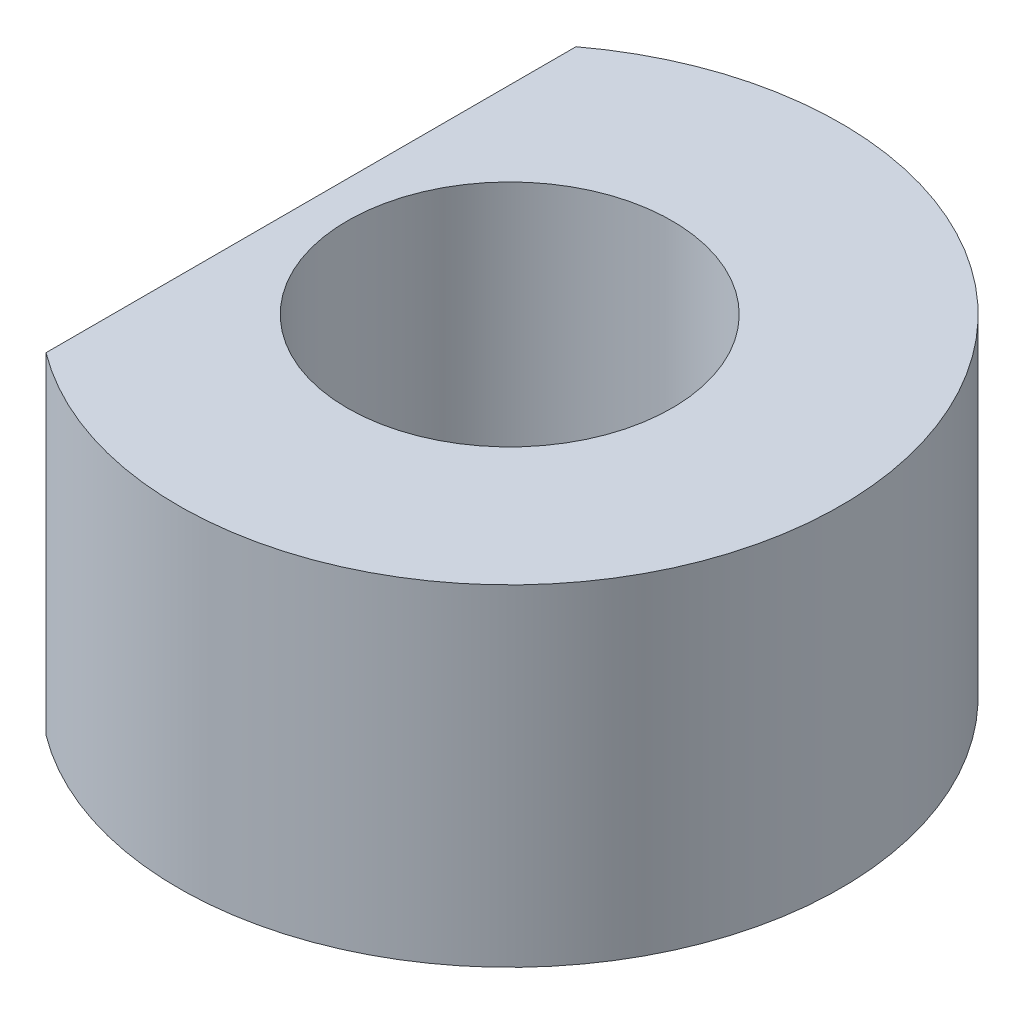
SolidWorks part; units mm, degrees
ref_plane "Front Plane" through (0, 0, 0) normal (0, 0, 1) x (1, 0, 0)
ref_plane "Top Plane" through (0, 0, 0) normal (0, 1, 0) x (1, 0, 0)
ref_plane "Right Plane" through (0, 0, 0) normal (1, 0, 0) x (0, 0, -1)
sketch "Sketch1" plane through (0, 0, 0) normal (0, 1, 0) x (1, 0, 0)
  line L0 (-3, 4) -> (-3, -4)
  arc A0 (-3, -4) -> (-3, 4) centre (0, 0) ccw
  dimension "D1" = 10
  dimension "D2" = 3
base flange "Base-Flange1" sketch "Sketch1" thickness 5 reverse thickness direction no parameters "D1"=0.7366
sketch "Sketch7" plane through (0, 0, 0) normal (0, 1, 0) x (1, 0, 0)
  circle A0 centre (0, 0) radius 2.45
  dimension "D1" = 4.9
extrude "Cut-Extrude1" cut sketch "Sketch7" against normal through all normal cut yes
sketch "Bend-Lines1" plane through (0, 0, 0) normal (0, 1, 0) x (1, 0, 0)
sketch "Bounding-Box1" plane through (0, 0, 0) normal (0, 1, 0) x (1, 0, 0)
sheet metal parameters "Sheet-Metal1" thickness 5 parameters "D1"=0.7366
flat pattern "Flat-Pattern1"
sketch "Bend-Lines2" plane through (0, 0, 0) normal (0, 1, 0) x (1, 0, 0)
sketch3d "Bounding-Box2"
  line L0 (-3, 4.9999, 0) -> (-3, -5, 0) construction
  line L1 (4.9999, 4.9999, 0) -> (4.9999, -5, 0) construction
  line L2 (-3, 4.9999, 0) -> (4.9999, 4.9999, 0) construction
  line L3 (-3, -5, 0) -> (4.9999, -5, 0) construction
sheet metal parameters "Sheet-Metal3" thickness 5 parameters "D1"=0.7366
flat pattern "Flat-Pattern1"
sketch "Bend-Lines2" plane through (0, 0, 0) normal (0, 1, 0) x (1, 0, 0)
sketch3d "Bounding-Box2"
  line L0 (-3, 4.9999, 0) -> (-3, -5, 0) construction
  line L1 (4.9999, 4.9999, 0) -> (4.9999, -5, 0) construction
  line L2 (-3, 4.9999, 0) -> (4.9999, 4.9999, 0) construction
  line L3 (-3, -5, 0) -> (4.9999, -5, 0) construction
